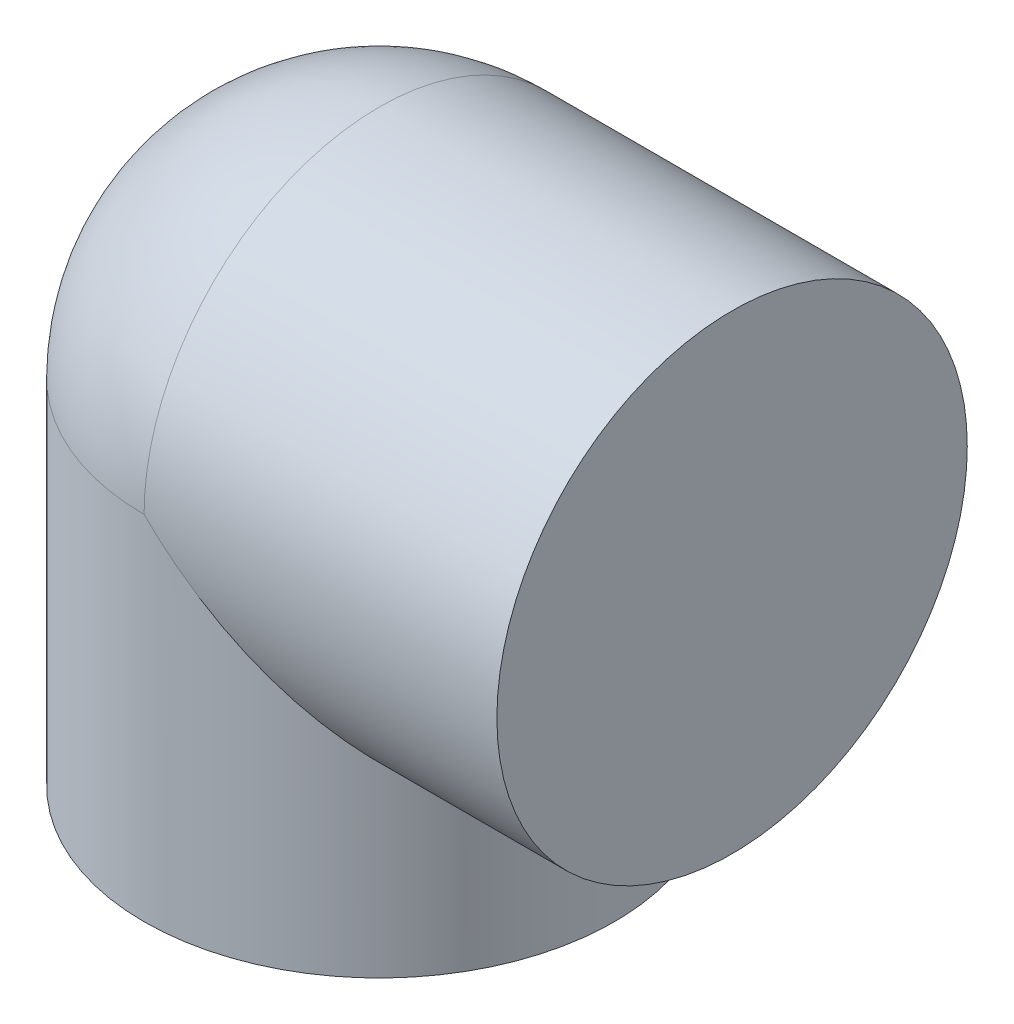
SolidWorks part; units mm, degrees
ref_plane "Front Plane" through (0, 0, 0) normal (0, 0, 1) x (1, 0, 0)
ref_plane "Top Plane" through (0, 0, 0) normal (0, 1, 0) x (1, 0, 0)
ref_plane "Right Plane" through (0, 0, 0) normal (1, 0, 0) x (0, 0, -1)
sketch "Sketch4" plane through (0, 50, 0) normal (0, 1, 0) x (1, 0, 0)
  line L0 (0, 20) -> (0, -20)
  arc A0 (0, 20) -> (0, -20) centre (0, 0) ccw
extrude "Boss-Extrude3" add sketch "Sketch4" along normal blind 50
fillet "Fillet1" radius 20 1 edges at (-20, 100, 0) conic radius 20
sketch "Sketch5" plane through (0, 0, 0) normal (1, 0, 0) x (0, 0, -1)
  circle A0 centre (0, 80) radius 20
extrude "Boss-Extrude4" add sketch "Sketch5" along normal blind 30
sketch "Sketch6" plane through (0, 50, 0) normal (0, 1, 0) x (1, 0, 0)
  line L0 (0, -20) -> (0, 20) construction
  line L1 (0, 20) -> (0, -20)
  arc A0 (0, -20) -> (0, 20) centre (0, 0) ccw
extrude "Boss-Extrude5" add sketch "Sketch6" along normal blind 30
